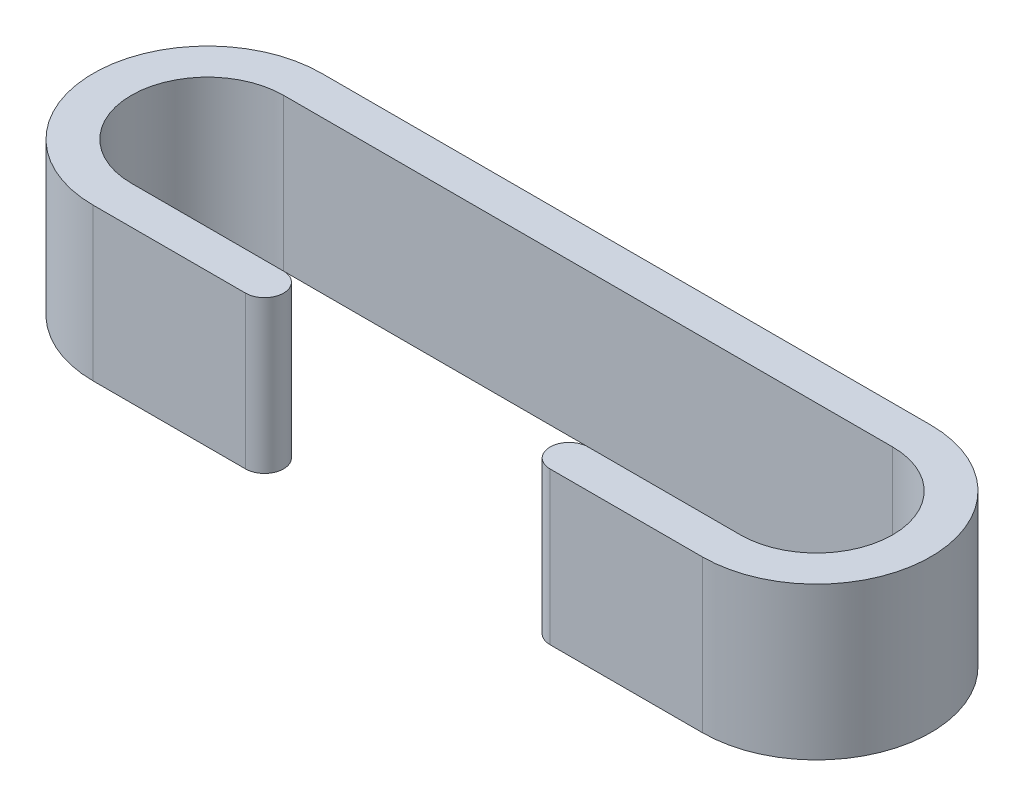
SolidWorks part; units mm, degrees
ref_plane "Front Plane" through (0, 0, 0) normal (0, 0, 1) x (1, 0, 0)
ref_plane "Top Plane" through (0, 0, 0) normal (0, 1, 0) x (1, 0, 0)
ref_plane "Right Plane" through (0, 0, 0) normal (1, 0, 0) x (0, 0, -1)
sketch "Sketch1" plane through (0, 0, 0) normal (0, 1, 0) x (1, 0, 0)
  line L0 (-6.35, 0) -> (-12.7, 0)
  line L1 (-12.7, 6.35) -> (12.7, 6.35)
  line L2 (12.7, 0) -> (6.35, 0)
  line L3 (-6.35, 0) -> (6.35, 0) construction
  line L4 (-6.35, -1.5875) -> (-12.7, -1.5875)
  line L5 (-12.7, 7.9375) -> (12.7, 7.9375)
  line L6 (12.7, -1.5875) -> (6.35, -1.5875)
  arc A0 (-12.7, 0) -> (-12.7, 6.35) centre (-12.7, 3.175) cw
  arc A1 (12.7, 6.35) -> (12.7, 0) centre (12.7, 3.175) cw
  arc A2 (-12.7, -1.5875) -> (-12.7, 7.9375) centre (-12.7, 3.175) cw
  arc A3 (12.7, 7.9375) -> (12.7, -1.5875) centre (12.7, 3.175) cw
  arc A4 (-6.35, 0) -> (-6.35, -1.5875) centre (-6.35, -0.7937) cw
  arc A5 (6.35, 0) -> (6.35, -1.5875) centre (6.35, -0.7937) ccw
  point P8 (0, 0)
  dimension "D1" = 25.4
  dimension "D2" = 6.35
  dimension "D3" = 12.7
  dimension "D4" = 1.5875
extrude "Boss-Extrude1" add sketch "Sketch1" along normal blind 6.35
